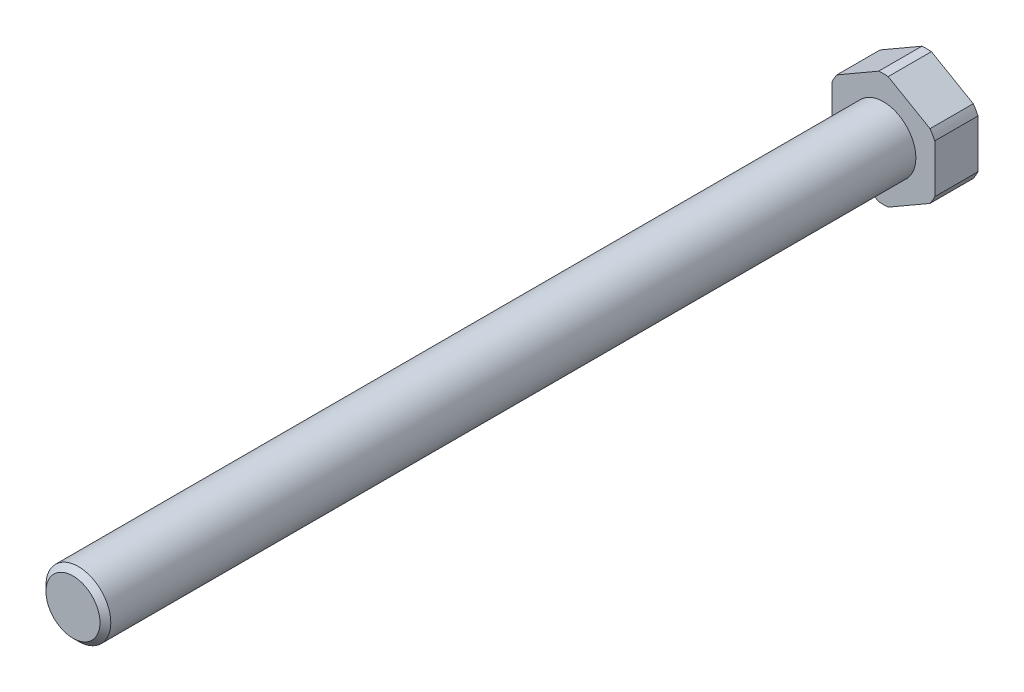
SolidWorks part; units mm, degrees
material "Сталь 20 ГОСТ 535-88"
ref_plane "Plane1" through (0, 0, 0) normal (0, 0, 1) x (1, 0, 0)
ref_plane "Plane2" through (0, 0, 0) normal (0, 1, 0) x (1, 0, 0)
ref_plane "Plane3" through (0, 0, 0) normal (1, 0, 0) x (0, 0, -1)
sketch "Эскиз1" plane through (0, 0, 0) normal (0, 0, 1) x (1, 0, 0)
  line L0 (0, 16) -> (0, -16) construction
  line L1 (-13, 0) -> (15, 0) construction
  circle A0 centre (0, 0) radius 10.5
  dimension "D1" = 21
extrude "Основание-Вытянуть" add sketch "Эскиз1" along normal blind 8
sketch "Эскиз2" plane through (0, 0, 8) normal (0, 0, 1) x (1, 0, 0)
  line L0 (0, 11) -> (0, -12) construction
  line L1 (-12, 0) -> (12, 0) construction
  line L2 (-9.5, 4.4721) -> (-9.5, -4.4721)
  circle A1 centre (0, 0) radius 10.5
  arc A2 (-9.5, 4.4721) -> (-9.5, -4.4721) centre (0, 0) ccw
  dimension "D2" = 9.5
  dimension "D1" = 0
extrude "Вырез-Вытянуть1" cut sketch "Эскиз2" against normal through all
ref_axis "Ось1" through (0, 0, 58) along (0, 0, -1)
pattern_circular "Круговой массив1" count 6 over 360 about axis through (0, 0, 58) along (0, 0, -1) of "Вырез-Вытянуть1"
sketch "Эскиз3" plane through (0, 0, 8) normal (0, 0, 1) x (1, 0, 0)
  circle A0 centre (0, 0) radius 6
  dimension "D1" = 12
extrude "Бобышка-Вытянуть1" add sketch "Эскиз3" along normal blind 150
chamfer "Фаска1" distance 1 angle 45 1 edges at (6, 0, 158)
